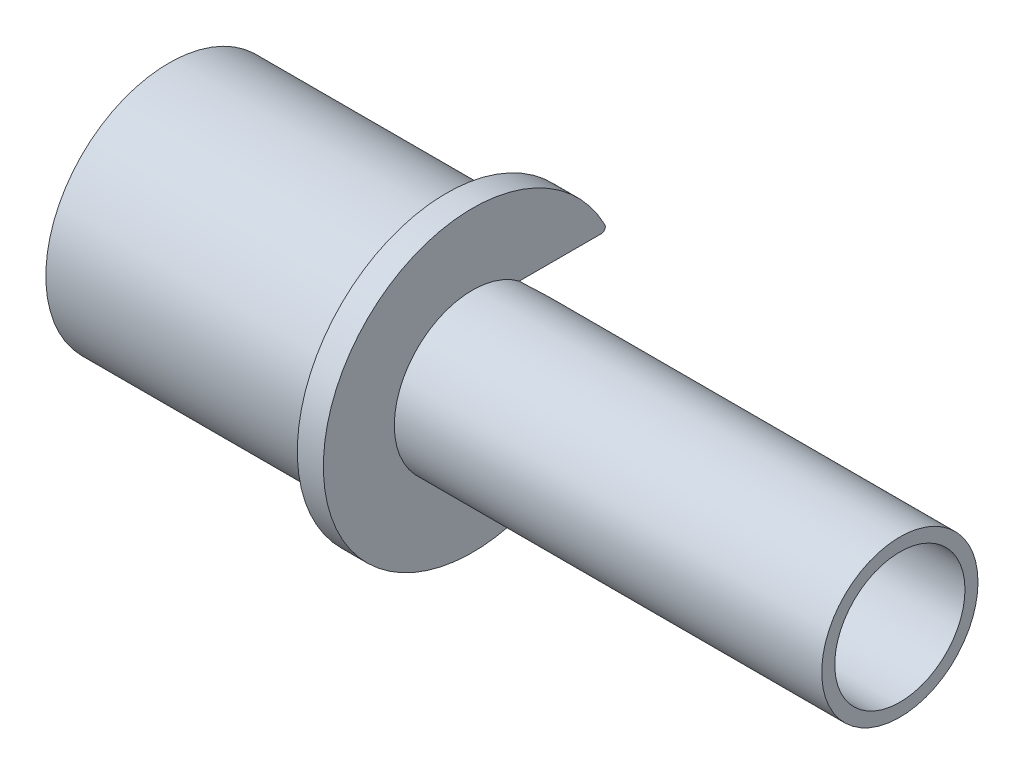
SolidWorks part; units mm, degrees
material "6061-T6 (SS)"
ref_plane "Front Plane" through (0, 0, 0) normal (0, 0, 1) x (1, 0, 0)
ref_plane "Top Plane" through (0, 0, 0) normal (0, 1, 0) x (1, 0, 0)
ref_plane "Right Plane" through (0, 0, 0) normal (1, 0, 0) x (0, 0, -1)
sketch "Sketch1" plane through (0, 0, 0) normal (0, 0, 1) x (1, 0, 0)
  line L0 (0, 0) -> (-16.6687, 0) construction
  line L1 (2.2375, 3.9687) -> (2.2375, 4.7625)
  line L2 (2.2375, 4.7625) -> (-23.8125, 4.7625)
  line L3 (-23.8125, 4.7625) -> (-23.8125, 9.0875)
  line L4 (-23.8125, 9.0875) -> (-25.4, 9.0875)
  line L5 (-25.4, 9.0875) -> (-25.4, 7.5)
  line L6 (-25.4, 7.5) -> (-42.315, 7.5)
  line L7 (-42.315, 7.5) -> (-42.315, 3.9687)
  line L8 (-42.315, 3.9687) -> (2.2375, 3.9687)
  line L9 (-25.4, -15.27) -> (-25.4, 15.27) construction
  line L10 (-50.8, -5.5563) -> (-50.8, 5.5562) construction
  line L14 (2.2375, -11.375) -> (2.2375, 11.375) construction
  dimension "D1" = 7.9375
  dimension "D4" = 15
  dimension "D3" = 9.525
  dimension "D2" = 1.5875
  dimension "D5" = 1.5875
  dimension "D6" = 8.485
revolve "Revolve1" add sketch "Sketch1" angle 360 about L0
sketch "Sketch2" plane through (2.2375, 0, 0) normal (1, 0, 0) x (0, 0, -1)
  line L0 (1.3441, 3.7342) -> (8.2848, 3.7342)
  line L1 (8.2848, -3.7342) -> (1.3441, -3.7342)
  line L2 (0, 0) -> (14.3216, 0) construction
  circle A0 centre (0, 0) radius 3.9687 construction
  circle A1 centre (0, 0) radius 9.0875 construction
  arc A2 (1.3441, 3.7342) -> (1.3441, -3.7342) centre (0, 0) cw
  arc A3 (8.2848, 3.7342) -> (8.2848, -3.7342) centre (0, 0) cw
  arc A4 (3.6742, 3.7342) -> (3.6742, -3.7342) centre (0, 0) cw construction
  circle A5 centre (5.2387, 0) radius 1.27 construction
  circle A6 centre (4.623, 2.4642) radius 1.27 construction
  circle A7 centre (4.623, -2.4642) radius 1.27 construction
  dimension "D1" = 1.27
  dimension "D2" = 2.54
extrude "Cut-Extrude1" [suppressed] cut sketch "Sketch2" against normal through all both
sketch "Sketch3" plane through (0, 0, 0) normal (0, 0, 1) x (1, 0, 0)
  line L0 (-42.315, 3.81) -> (-42.315, -3.81)
  line L1 (-42.315, 7.5) -> (-42.315, -7.5) construction
  line L2 (-42.315, -3.81) -> (-23.8125, -3.81)
  line L4 (-23.8125, 3.81) -> (-42.315, 3.81)
  line L5 (-20.6375, -0.635) -> (-20.6375, 0.635)
  line L6 (-20.6375, 0) -> (0, 0) construction
  line L8 (-23.8125, -9.0875) -> (-23.8125, 9.0875) construction
  arc A1 (-23.8125, -3.81) -> (-20.6375, -0.635) centre (-23.8125, -0.635) ccw
  arc A2 (-20.6375, 0.635) -> (-23.8125, 3.81) centre (-23.8125, 0.635) ccw
  dimension "D1" = 7.62
  dimension "D2" = 3.175
extrude "Cut-Extrude2" cut sketch "Sketch3" against normal up to next
fillet "Fillet1" radius 0.254 4 edges at (-24.6062, 3.81, -8.2502) (-24.6062, -3.81, -8.2502) (-33.8575, -3.81, -6.4602) (-33.8575, 3.81, -6.4602)
equation "\"bearing1\"=0.273438"
equation "\"D1@Sketch1\"=5/16"
equation "\"D4@Sketch1\"=15mm"
equation "\"D6@Sketch1\"=.275+1.5mm"
